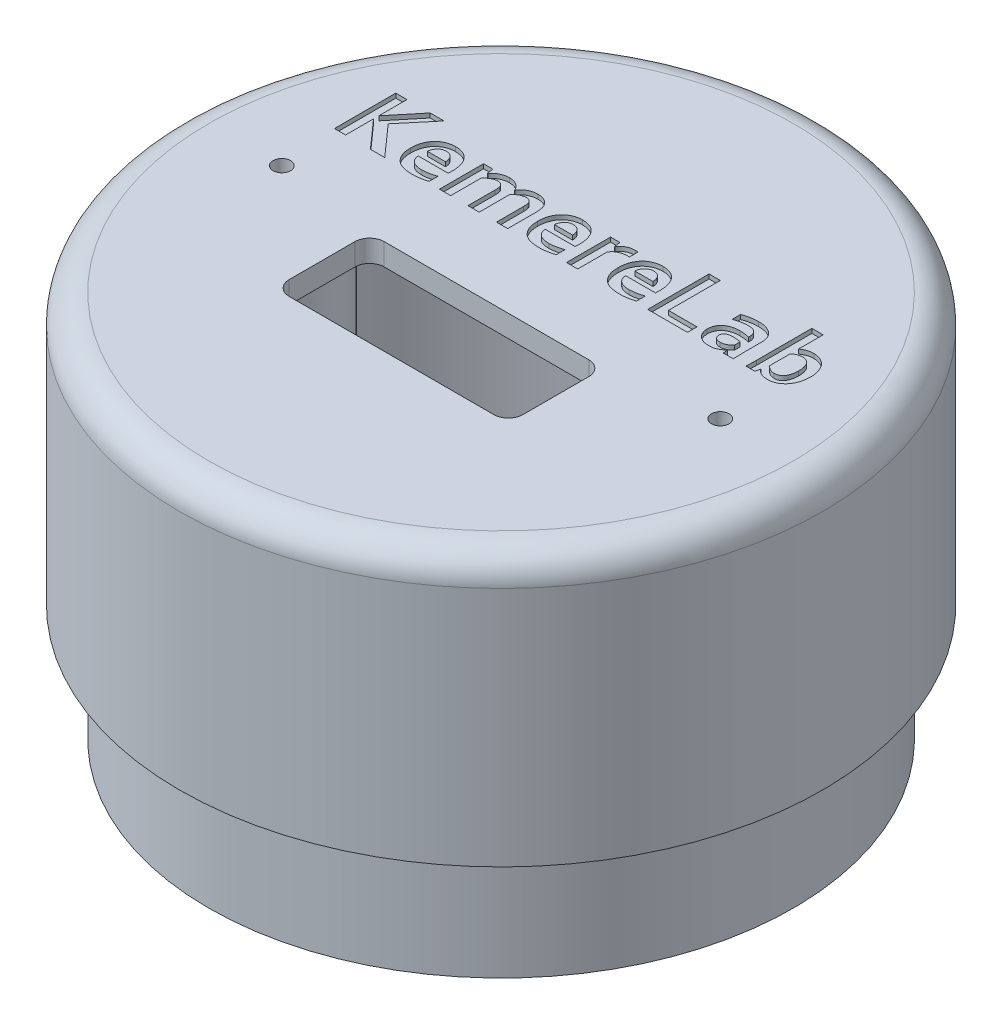
SolidWorks part; units mm, degrees
ref_plane "Front Plane" through (0, 0, 0) normal (0, 0, 1) x (1, 0, 0)
ref_plane "Top Plane" through (0, 0, 0) normal (0, 1, 0) x (1, 0, 0)
ref_plane "Right Plane" through (0, 0, 0) normal (1, 0, 0) x (0, 0, -1)
sketch "Sketch1" plane through (0, 0, 0) normal (0, 1, 0) x (1, 0, 0)
  line L0 (0, 0) -> (0, 22) construction
  line L1 (14.5, -6.5) -> (-14.5, -6.5)
  line L2 (-14.5, -6.5) -> (-14.5, -10.5)
  line L3 (-14.5, -10.5) -> (14.5, -10.5)
  line L4 (14.5, -10.5) -> (14.5, -6.5)
  line L5 (-11, -6.5) -> (-11, -7.5)
  line L6 (11, -6.5) -> (11, -7.5)
  line L7 (-8, -6.5) -> (-8, -7.5)
  line L8 (8, -1) -> (-8, -1)
  line L9 (-11, -9.5) -> (-11, -10.5)
  line L10 (11, -9.5) -> (11, -10.5)
  line L11 (8, -1) -> (8, -6.5)
  line L12 (8, -6.5) -> (-8, -6.5)
  line L13 (-13.5, -7.5) -> (13.5, -7.5)
  line L14 (-13.5, -7.5) -> (-13.5, -9.5)
  line L15 (-13.5, -9.5) -> (13.5, -9.5)
  line L16 (13.5, -7.5) -> (13.5, -9.5)
  line L17 (-13.5, -7.5) -> (13.5, -9.5) construction
  line L18 (-13.5, -9.5) -> (13.5, -7.5) construction
  line L19 (-8, -1) -> (-8, -6.5)
  line L20 (8, -1) -> (-8, -6.5) construction
  line L21 (8, -6.5) -> (-8, -1) construction
  line L22 (8, -6.5) -> (8, -7.5)
  circle A0 centre (-15, 0) radius 2.15
  circle A1 centre (0, 0) radius 20.5
  circle A2 centre (0, 0) radius 3.9639
  circle A3 centre (-15, 0) radius 0.6
  circle A4 centre (0, 0) radius 18.5
  circle A5 centre (0, 0) radius 20
  circle A6 centre (-15, 0) radius 3.6
  circle A7 centre (15, 0) radius 3.6
  circle A8 centre (15, 0) radius 2.15
  circle A9 centre (15, 0) radius 0.6
  circle A10 centre (0, 0) radius 22
  circle A14 centre (0, 0) radius 5.5
  point P8 (0, 0)
  point P28 (0, -3.75)
  point P44 (0, 0)
  point P46 (0, -8.5)
  dimension "D1" = 1
  dimension "D2" = 1
  dimension "D8" = 3.5
  dimension "D10" = 4.3
  dimension "D3" = 15
  dimension "D11" = 1.2
  dimension "D12" = 15
  dimension "D13" = 16
  dimension "D4" = 27
  dimension "D5" = 2
  dimension "D6" = 1
  dimension "D7" = 1
  dimension "D9" = 3.5
  dimension "D14" = 6.5
extrude "Boss-Extrude1" add sketch "Sketch1" along normal blind 1.5 contours A10
extrude "Boss-Extrude4" add sketch "Sketch1<15>" against normal blind 17 contours A10 A1 | A1 A5 region at (-20.442, 0, 0) region at (-21.3777, 0, 0)
sketch "Sketch1<15>" plane through (0, 0, 0) normal (0, 1, 0) x (1, 0, 0) same geometry as "Sketch1"
extrude "Boss-Extrude5" add sketch "Sketch1<16>" against normal blind 25 contours A5 A4 region at (-19.4343, 0, 0)
sketch "Sketch1<16>" plane through (0, 0, 0) normal (0, 1, 0) x (1, 0, 0) same geometry as "Sketch1"
extrude "Boss-Extrude7" add sketch "Sketch1<18>" against normal blind 10 contours A6 A0 | A7 A8 | A6 | A7 region at (18.393, 0, 0.4653) region at (-14.5414, 0, -3.4687)
sketch "Sketch1<18>" plane through (0, 0, 0) normal (0, 1, 0) x (1, 0, 0) same geometry as "Sketch1"
extrude "Cut-Extrude3" cut sketch "Sketch1<19>" against normal blind 10 contours A0 A3 | A8 A9 region at (-17.0892, 0, 0) region at (12.9108, 0, 0)
sketch "Sketch1<19>" plane through (0, 0, 0) normal (0, 1, 0) x (1, 0, 0) same geometry as "Sketch1"
extrude "Cut-Extrude4" cut sketch "Sketch1<20>" against normal blind 10 and the other way blind 10 contours A3 | A9 region at (-15, 0, 0) region at (15, 0, 0)
sketch "Sketch1<20>" plane through (0, 0, 0) normal (0, 1, 0) x (1, 0, 0) same geometry as "Sketch1"
extrude "Boss-Extrude8" add sketch "Sketch1<21>" against normal blind 5 contours L15 L14 L13 L5 L1 L2 L3 L9 | L13 L16 L15 L10 L3 L4 L1 L6 region at (14.4468, 0, 8.5) region at (-12.75, 0, 10.4468)
sketch "Sketch1<21>" plane through (0, 0, 0) normal (0, 1, 0) x (1, 0, 0) same geometry as "Sketch1"
extrude "Cut-Extrude6" cut sketch "Sketch1<22>" along normal blind 5 contours A14 L8 L19 L1 L11 | L8 A14 A2 | L8 A2 | L22 L1 L7 L13 region at (0, 0, 7) region at (0, 0, 6.3308) region at (0, 0, 5.3828) region at (0, 0, 2.2343)
sketch "Sketch1<22>" plane through (0, 0, 0) normal (0, 1, 0) x (1, 0, 0) same geometry as "Sketch1"
fillet "Fillet13" radius 1 4 edges at (8, 0.75, 1) (-8, 0.75, 1) (8, 0.75, 7.5) (-8, 0.75, 7.5)
fillet "Fillet14" radius 2 1 edges at (0, 1.5, 22)
sketch "Sketch2" plane through (0, 1.5, 0) normal (0, 1, 0) x (1, 0, 0)
  text T0 "KemereLab" font "Corbel" height in points 16
extrude "Cut-Extrude7" cut sketch "Sketch2" against normal blind 0.3
